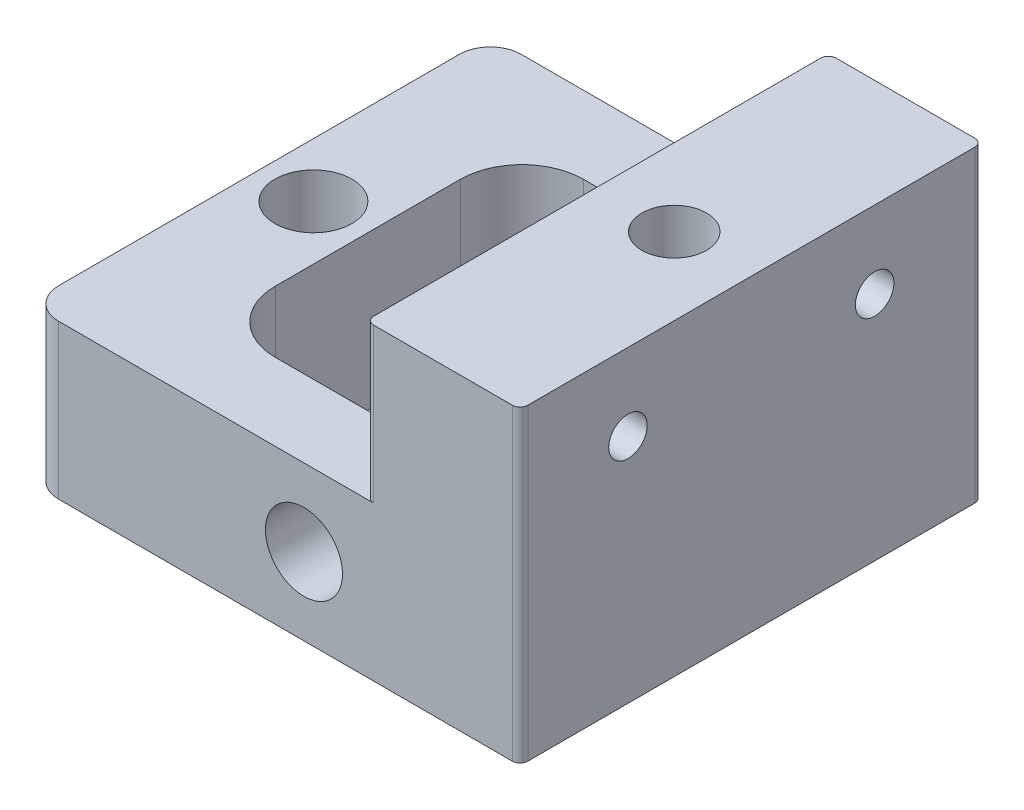
SolidWorks part; units mm, degrees
material "AISI 1045 Steel, cold drawn"
ref_plane "Front Plane" through (0, 0, 0) normal (0, 0, 1) x (1, 0, 0)
ref_plane "Top Plane" through (0, 0, 0) normal (0, 1, 0) x (1, 0, 0)
ref_plane "Right Plane" through (0, 0, 0) normal (1, 0, 0) x (0, 0, -1)
sketch "Sketch1" plane through (0, 0, 0) normal (0, 1, 0) x (1, 0, 0)
  line L1 (7.44, -10) -> (-7.44, -10)
  line L2 (7.44, -10) -> (7.44, 10)
  line L3 (7.44, 10) -> (-7.44, 10)
  line L4 (-7.44, -10) -> (-7.44, 10)
  line L5 (7.44, -10) -> (-7.44, 10) construction
  line L6 (7.44, 10) -> (-7.44, -10) construction
  line L7 (17.44, -15) -> (-14.49, -15)
  line L8 (17.44, -15) -> (17.44, 15)
  line L9 (17.44, 15) -> (-14.49, 15)
  line L10 (-14.49, -15) -> (-14.49, 15)
  line L11 (17.44, -15) -> (-14.49, 15) construction
  line L12 (17.44, 15) -> (-14.49, -15) construction
  point P0 (0, 0)
  point P6 (1.475, 0)
  dimension "D1" = 14.88
  dimension "D2" = 20
  dimension "D3" = 7.05
  dimension "D4" = 5
  dimension "D5" = 10
extrude "Boss-Extrude1" add sketch "Sketch1" along normal blind 10
sketch "Sketch2" plane through (0, 10, 0) normal (0, 1, 0) x (1, 0, 0)
  line L0 (-14.49, -15) -> (17.44, -15) construction
  line L1 (17.44, 15) -> (7.44, 15)
  line L2 (17.44, 15) -> (17.44, -15)
  line L3 (17.44, -15) -> (7.44, -15)
  line L4 (7.44, 15) -> (7.44, -15)
  line L5 (7.44, -10) -> (7.44, 10) construction
extrude "Boss-Extrude2" add sketch "Sketch2" along normal blind 10
hole_wizard "Tap Drill for M5x0.8 Tap1" positions "Sketch3" profile "Sketch4" hole size "M5x0.8" standard "ANSI Metric" end condition through all
sketch "Sketch3" plane through (0, 20, 0) normal (0, 1, 0) x (1, 0, 0)
  line L1 (17.44, 15) -> (7.44, -15) construction
  point P0 (12.44, 0)
sketch "Sketch4" plane through (12.44, 20, 0) normal (1, 0, 0) x (0, 0, 1)
  line L0 (0, 0) -> (0, 20)
  line L1 (0, 20) -> (2.1, 20)
  line L2 (2.1, 20) -> (2.1, 0)
  line L5 (2.1, 0) -> (0, 0)
  line L11 (0, -6.35) -> (0, 107.95) construction
  dimension "Thru Hole Dia." = 4.2
  dimension "Thru Hole Depth" = 20
fillet "Fillet2" radius 4 4 edges at (-7.44, 5, 10) (-7.44, 5, -10) (7.44, 5, -10) (7.44, 5, 10)
sketch "Sketch5" plane through (0, 0, -15) normal (0, 0, 1) x (1, 0, 0)
  line L0 (7.44, 10) -> (7.44, 0) construction
  line L1 (3.44, 10) -> (-3.44, 10) construction
  circle A0 centre (3.42, 5) radius 2.5
  dimension "D2" = 5
  dimension "D1" = 4.02
  dimension "D3" = 5
extrude "Cut-Extrude2" cut sketch "Sketch5" along normal through all
fillet "Fillet3" radius 2 2 edges at (-14.49, 5, -15) (-14.49, 5, 15)
fillet "Fillet4" radius 0.5 4 edges at (17.44, 10, 15) (17.44, 10, -15) (7.44, 15, -15) (7.44, 15, 15)
hole_wizard "Tap Drill for M3x0.5 Tap1" positions "Sketch8" profile "Sketch9" hole size "M3x0.5" standard "ANSI Metric" end condition through all
sketch "Sketch8" plane through (7.44, 0, 0) normal (-1, 0, 0) x (0, 0, 1)
  line L0 (-8, 15) -> (8, 15) construction
  line L2 (-14.5, 20) -> (14.5, 20) construction
  line L3 (-14.5, 20) -> (-14.5, 10) construction
  point P1 (-8, 15)
  point P2 (8, 15)
  point P7 (0, 20)
  point P8 (0, 15)
  point P11 (-14.5, 15)
  dimension "D1" = 16
sketch "Sketch9" plane through (7.44, 15, -8) normal (0, 1, 0) x (0, 0, 1)
  line L0 (0, 0) -> (0, 10)
  line L1 (0, 10) -> (1.25, 10)
  line L2 (1.25, 10) -> (1.25, 0)
  line L5 (1.25, 0) -> (0, 0)
  line L11 (0, -6.35) -> (0, 107.95) construction
  dimension "Thru Hole Dia." = 2.5
  dimension "Thru Hole Depth" = 10
hole_wizard "Ø5.0 (5) Diameter Hole1" positions "Sketch10" profile "Sketch11" hole size "Ø5.0" standard "ANSI Metric" end condition through all
sketch "Sketch10" plane through (0, 10, 0) normal (0, 1, 0) x (1, 0, 0)
  line L0 (-14.49, 0) -> (-7.44, 0) construction
  line L1 (-14.49, 13) -> (-14.49, -13) construction
  line L2 (-7.44, 6) -> (-7.44, -6) construction
  point P0 (-10.965, 0)
  point P14 (-10.965, 0)
sketch "Sketch11" plane through (-10.965, 10, 0) normal (1, 0, 0) x (0, 0, 1)
  line L0 (0, 0) -> (0, 10)
  line L1 (0, 10) -> (2.5, 10)
  line L2 (2.5, 10) -> (2.5, 0)
  line L5 (2.5, 0) -> (0, 0)
  line L11 (0, -6.35) -> (0, 107.95) construction
  dimension "Thru Hole Dia." = 5
  dimension "Thru Hole Depth" = 10
